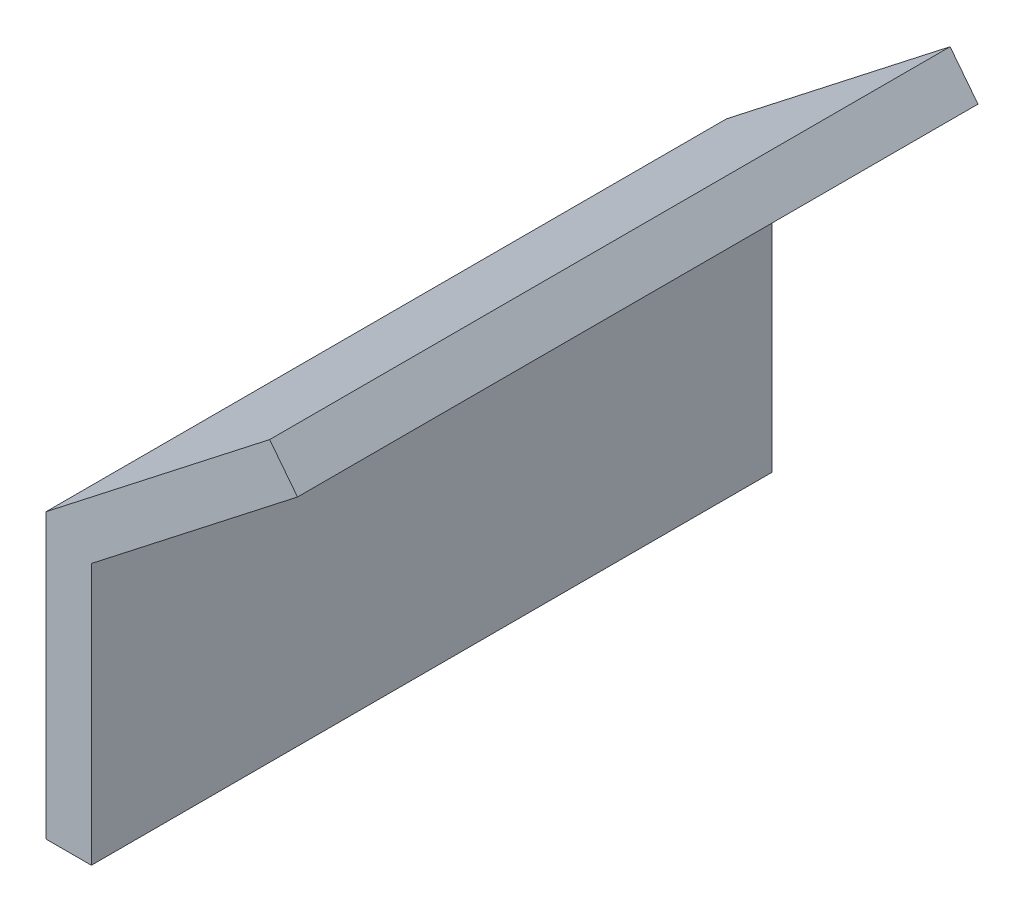
SolidWorks part; units mm, degrees
material "PLA"
ref_plane "Front Plane" through (0, 0, 0) normal (0, 0, 1) x (1, 0, 0)
ref_plane "Top Plane" through (0, 0, 0) normal (0, 1, 0) x (1, 0, 0)
ref_plane "Right Plane" through (0, 0, 0) normal (1, 0, 0) x (0, 0, -1)
sketch "Sketch1" plane through (0, 0, 0) normal (0, 0, 1) x (1, 0, 0)
  line L0 (0, 0) -> (39.4381, 30.7349)
  line L1 (0, 0) -> (0, -50)
  line L2 (8, -3.9079) -> (44.3557, 24.4248)
  line L3 (8, -3.9079) -> (8, -50)
  line L4 (39.4381, 30.7349) -> (44.3557, 24.4248)
  line L5 (0, -50) -> (8, -50)
  dimension "D1" = 50
  dimension "D2" = 50
  dimension "D3" = 127.93
  dimension "D4" = 8
extrude "Boss-Extrude1" add sketch "Sketch1" along normal mid plane 120
